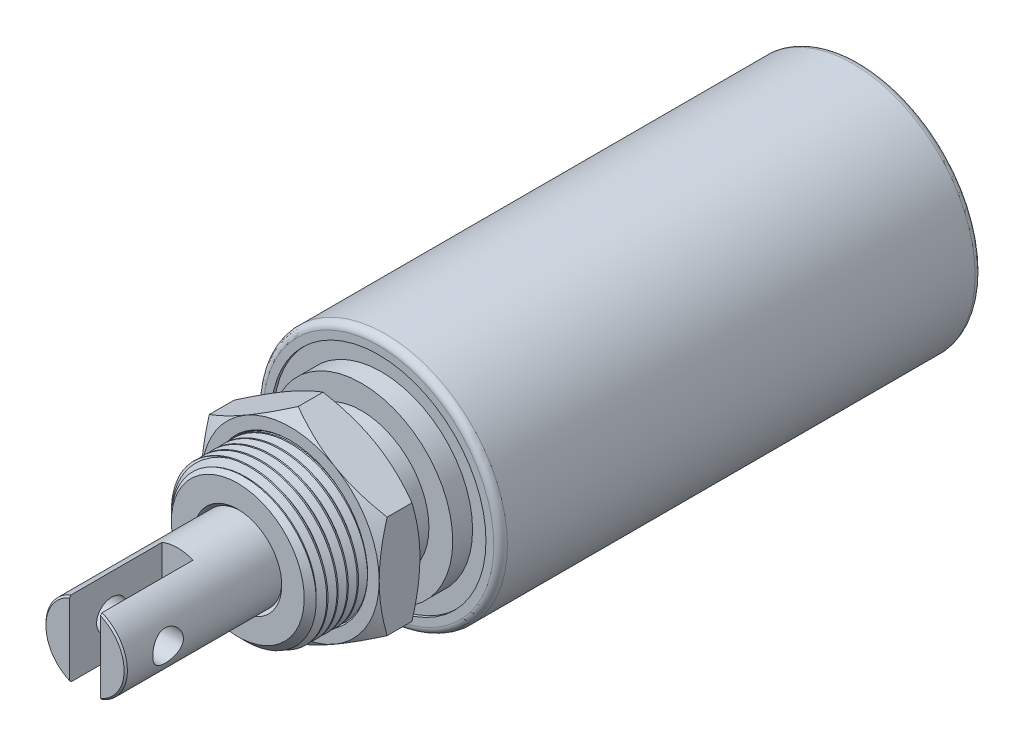
SolidWorks part; units mm, degrees
ref_plane "Front Plane" through (0, 0, 0) normal (0, 0, 1) x (1, 0, 0)
ref_plane "Top Plane" through (0, 0, 0) normal (0, 1, 0) x (1, 0, 0)
ref_plane "Right Plane" through (0, 0, 0) normal (1, 0, 0) x (0, 0, -1)
sketch "Sketch0" plane through (0, 0, 0) normal (1, 0, 0) x (0, 0, -1)
  line L0 (0, 0) -> (39.083, 0) construction
  line L1 (0, 0) -> (-21.5646, 0) construction
  line L2 (39.083, 9.525) -> (39.083, -9.525) construction
  line L3 (0, 5.9436) -> (0, -5.9436) construction
  line L4 (-21.5646, 3.175) -> (-21.5646, -3.175) construction
  line L5 (-21.5646, 0) -> (-34.2646, 0) construction
  point P10 (-18.2626, 0)
  point P12 (-9.652, 0)
  dimension "D1" = 18.2626
  dimension "Lg." = 39.083
  dimension "Dia." = 19.05
  dimension "Rod Dia." = 6.35
  dimension "A" = 21.5646
  dimension "Thread OD" = 11.8872
  dimension "Stroke" = 12.7
  dimension "D2" = 3.302
  dimension "D3" = 9.652
sketch "Sketch1" plane through (0, 0, 0) normal (1, 0, 0) x (0, 0, -1)
  line L0 (39.083, 0) -> (0, 0) construction
  line L1 (38.3286, 9.525) -> (1.8542, 9.525)
  line L2 (39.083, 2.0066) -> (39.083, 0)
  line L3 (39.083, 0) -> (0, 0)
  line L4 (1.5494, 8.382) -> (1.5494, 7.112)
  line L5 (38.862, 2.2276) -> (38.862, 8.9916)
  line L6 (1.3208, 8.9916) -> (1.3208, 8.382)
  line L7 (1.3208, 8.382) -> (1.5494, 8.382)
  line L8 (1.5494, 7.112) -> (0, 7.112)
  line L9 (0, 7.112) -> (0, 0)
  arc A0 (39.083, 2.0066) -> (38.862, 2.2276) centre (38.862, 2.0066) ccw
  arc A1 (38.862, 8.9916) -> (38.3286, 9.525) centre (38.3286, 8.9916) ccw
  arc A2 (1.3208, 8.9916) -> (1.8542, 9.525) centre (1.8542, 8.9916) cw
  dimension "D1" = 0.5334
  dimension "D4" = 1.3208
  dimension "D2" = 0.221
  dimension "D3" = 4.0132
  dimension "D5" = 16.764
  dimension "D6" = 0.2286
  dimension "D7" = 14.224
revolve "Revolve1" add sketch "Sketch1" angle 360 mid plane about L0
sketch "Sketch2" plane through (0, 0, 0) normal (1, 0, 0) x (0, 0, -1)
  line L0 (0, 0) -> (-21.5646, 0) construction
  line L3 (-9.652, 3.429) -> (-9.652, 5.1816)
  line L4 (-9.652, 5.1816) -> (-8.89, 5.9436)
  line L5 (-8.89, 5.9436) -> (-2.3114, 5.9436)
  line L6 (-2.3114, 5.9436) -> (-1.6256, 5.2578)
  line L7 (-1.6256, 5.2578) -> (0, 5.2578)
  line L8 (0, 5.2578) -> (0, 3.175)
  line L9 (-9.398, 3.175) -> (0, 3.175)
  line L11 (-9.398, 3.175) -> (-9.652, 3.429)
  dimension "D1" = 1.6256
  dimension "D4" = 0.762
  dimension "D5" = 9.652
  dimension "D2" = 45
  dimension "D6" = 0.6858
  dimension "D3" = 45
  dimension "D8" = 0.254
  dimension "D7" = 45
revolve "Revolve2" add sketch "Sketch2" angle 360 mid plane about L0
sketch "Sketch3" plane through (0, 0, 0) normal (1, 0, 0) x (0, 0, -1)
  line L0 (-21.5646, 0) -> (0, 0) construction
  line L1 (-21.4376, 3.175) -> (-21.5646, 3.048)
  line L2 (0, 0) -> (-21.5646, 0)
  line L3 (0, 0) -> (0, 3.175)
  line L4 (0, 3.175) -> (-21.4376, 3.175)
  line L5 (-21.5646, 0) -> (-21.5646, 3.048)
  line L6 (-21.4376, 3.175) -> (-21.5646, 3.175) construction
  line L7 (-21.5646, 3.175) -> (-21.5646, 3.048) construction
  dimension "D1" = 0.127
revolve "Revolve3" add sketch "Sketch3" angle 360 mid plane about L2
sketch "Sketch4" plane through (0, 0, 0) normal (0, 1, 0) x (0, 0, -1)
  line L1 (-21.5646, 1.2065) -> (-14.351, 1.2065)
  line L2 (-21.5646, 1.2065) -> (-21.5646, -1.2065)
  line L3 (-21.5646, -1.2065) -> (-14.351, -1.2065)
  line L4 (-14.351, 1.2065) -> (-14.351, -1.2065)
  dimension "D1" = 2.413
  dimension "D2" = 7.2136
extrude "Cut-Extrude1" cut sketch "Sketch4" against normal up to surface and the other way up to surface up to face at (0, 3.175, 21.4376) other way up to face at (0, 3.175, 21.4376)
sketch "Sketch5" plane through (0, 0, 0) normal (1, 0, 0) x (0, -1, 0)
  line L0 (0, -21.5646) -> (0, -18.2626) construction
  circle A0 centre (0, -18.2626) radius 1.1938
  dimension "D1" = 2.3876
extrude "Cut-Extrude2" cut sketch "Sketch5" along normal up to surface and the other way up to surface up to face at (0, 0, 17.8943) other way up to face at (0, 0, 17.8943)
move or copy body "Body-Move/Copy1" bodies to move or copy 107 copy yes number of copies 1 translate (0, 0, 12.7)
sketch "SketchX" plane through (0, 0, 0) normal (1, 0, 0) x (0, 0, -1)
  line L0 (-34.1376, -2.9368) -> (-27.051, -2.9368) construction
  line L1 (-34.2646, 2.799) -> (-34.2646, -2.799) construction
  line L2 (-34.1376, 2.9368) -> (-27.051, 2.9368) construction
  line L7 (-27.051, 3.175) -> (-27.051, 2.9368) construction
  line L8 (-12.7, 3.175) -> (-27.051, 3.175) construction
  line L11 (-27.051, -2.9368) -> (-27.051, -3.175) construction
  line L12 (-27.051, -3.175) -> (-12.7, -3.175) construction
  line L13 (-34.1376, -2.9368) -> (-27.051, -2.9368)
  line L14 (-34.2646, 2.799) -> (-34.2646, -2.799)
  line L15 (-34.1376, 2.9368) -> (-27.051, 2.9368)
  line L16 (-27.051, 3.175) -> (-27.051, 2.9368)
  line L17 (-14.351, 3.175) -> (-27.051, 3.175)
  line L18 (-27.051, -2.9368) -> (-27.051, -3.175)
  line L19 (-27.051, -3.175) -> (-14.351, -3.175)
  line L20 (-14.351, 3.175) -> (-14.351, 2.9368) construction
  arc A1 (-34.2646, -2.799) -> (-34.1376, -2.9368) centre (4.056, 32.3945) ccw construction
  circle A2 centre (-30.9626, 0) radius 1.1938 construction
  arc A3 (-34.1376, 2.9368) -> (-34.2646, 2.799) centre (4.056, -32.3945) ccw construction
  arc A4 (-34.2646, -2.799) -> (-34.1376, -2.9368) centre (4.056, 32.3945) ccw
  circle A5 centre (-30.9626, 0) radius 1.1938
  arc A6 (-34.1376, 2.9368) -> (-34.2646, 2.799) centre (4.056, -32.3945) ccw
delete or keep bodies "Body-Delete1" type delete bodies bodies 108
sketch "Sketch10" plane through (0, 0, 0) normal (0, 0, 1) x (1, 0, 0)
  line L0 (0, 5.9436) -> (0, 6.9342) construction
  line L1 (0, 8.0069) -> (-6.9342, 4.0035)
  line L2 (-6.9342, 4.0035) -> (-6.9342, -4.0035)
  line L3 (-6.9342, -4.0035) -> (0, -8.0069)
  line L4 (0, -8.0069) -> (6.9342, -4.0035)
  line L5 (6.9342, -4.0035) -> (6.9342, 4.0035)
  line L6 (6.9342, 4.0035) -> (0, 8.0069)
  circle A0 centre (0, 0) radius 5.9436
  circle A1 centre (0, 0) radius 6.9342 construction
  dimension "D1" = 13.8684
extrude "Boss-Extrude3" add sketch "Sketch10" along normal blind 3.175 from offset 2.3813 separate body
sketch "Sketch11" plane through (0, 0, 0) normal (1, 0, 0) x (0, 0, -1)
  line L0 (-2.3813, 0) -> (-5.5563, 0) construction
  line L1 (-5.5563, 5.9436) -> (-5.5563, -5.9436) construction
  line L2 (-2.3813, -5.9436) -> (-2.3813, 5.9436) construction
  line L3 (-5.5563, 8.0069) -> (-5.5563, 6.9342)
  line L4 (-5.5563, 4.0035) -> (-5.5563, 8.0069) construction
  line L5 (-5.5563, 6.9342) -> (-4.9369, 8.0069)
  line L6 (-5.5563, 8.0069) -> (-2.3813, 8.0069) construction
  line L7 (-4.9369, 8.0069) -> (-5.5563, 8.0069)
  line L8 (-2.3813, 8.0069) -> (-2.3813, 6.9342)
  line L9 (-2.3813, 4.0035) -> (-2.3813, 8.0069) construction
  line L10 (-2.3813, 6.9342) -> (-3.0006, 8.0069)
  line L11 (-3.0006, 8.0069) -> (-2.3813, 8.0069)
  line L12 (0, 6.9342) -> (-5.5563, 6.9342) construction
  line L13 (-5.5563, 6.0295) -> (-5.5563, 5.9436)
  line L14 (-5.5563, 5.9436) -> (-5.4703, 5.9436)
  line L15 (-5.4703, 5.9436) -> (-5.5563, 6.0295)
  line L16 (-2.3813, 6.0295) -> (-2.3813, 5.9436)
  line L17 (-2.3813, 5.9436) -> (-2.4672, 5.9436)
  line L18 (-2.4672, 5.9436) -> (-2.3813, 6.0295)
  dimension "D1" = 30
  dimension "D2" = 0.0859
revolve "Cut-Revolve1" cut sketch "Sketch11" angle 360 about L0
sketch "Sketch6" plane through (0, 0, 9.652) normal (0, 0, 1) x (1, 0, 0)
  circle A1 centre (0, 0) radius 5.9436
  point P1 (0, 5.9436)
curve "Helix/Spiral1" pitch 0.7937 height 8.8201 radius 5.9436 centre (0, 0, 9.652) axis (0, 0, -1) start towards (0, 1, 0) parameters "Pitch"=0.7937
sketch "Sketch7" plane through (0, 0, 0) normal (1, 0, 0) x (0, 0, -1)
  line L0 (-10.3961, 6.0295) -> (-9.6024, 6.0295) construction
  line L1 (-9.6024, 6.0295) -> (-9.9993, 5.3421) construction
  line L2 (-9.9993, 5.3421) -> (-10.3961, 6.0295) construction
  line L3 (-10.0489, 5.428) -> (-9.9497, 5.428) construction
  line L4 (-10.3465, 5.9436) -> (-9.652, 5.9436) construction
  line L5 (-9.9993, 5.3421) -> (-9.9993, 5.428) construction
  line L6 (-9.9993, 5.9436) -> (-9.9993, 6.0295) construction
  line L7 (-10.0489, 5.428) -> (-9.9497, 5.428)
  line L8 (-9.9497, 5.428) -> (-9.6272, 5.9866)
  line L9 (-9.6272, 5.9866) -> (-10.3713, 5.9866)
  line L10 (-10.3713, 5.9866) -> (-10.0489, 5.428)
  line L11 (-9.9993, 5.3421) -> (-9.9993, -5.9436) construction
  line L12 (-9.9993, -5.9436) -> (-9.2055, -5.9436) construction
  line L13 (-9.2055, -5.9436) -> (-8.4118, -5.9436) construction
  line L14 (-8.4118, -5.9436) -> (-7.618, -5.9436) construction
  line L15 (-8.89, -5.9436) -> (-2.3114, -5.9436) construction
  point P15 (-9.9993, 5.9866)
  dimension "D1" = 0.7937
  dimension "D2" = 0.0992
sweep "Cut-Sweep1" cut profiles "Sketch7" path "Helix/Spiral1"
equation "\"D3@Helix/Spiral1\" = \"Pitch@Helix/Spiral1\" + \"D5@Sketch2\" - \"D1@Sketch2\""
equation "\"D1@Sketch7\" = \"Pitch@Helix/Spiral1\""
equation "\"D2@Sketch7\" = \"D1@Sketch7\" / 8"
